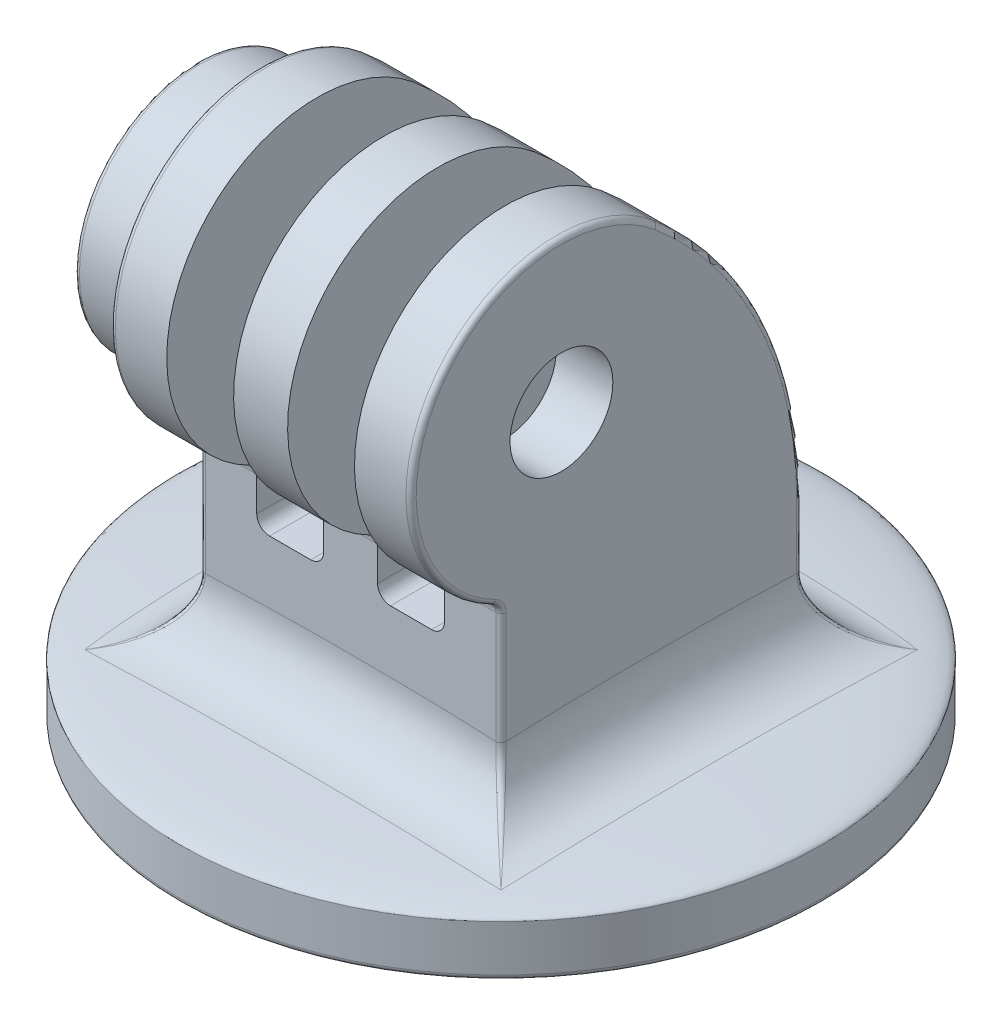
SolidWorks part; units mm, degrees
material "ABS"
ref_plane "Front Plane" through (0, 0, 0) normal (0, 0, 1) x (1, 0, 0)
ref_plane "Top Plane" through (0, 0, 0) normal (0, 1, 0) x (1, 0, 0)
ref_plane "Right Plane" through (0, 0, 0) normal (1, 0, 0) x (0, 0, -1)
sketch "Sketch1" plane through (0, 0, 0) normal (0, 1, 0) x (1, 0, 0)
  circle A0 centre (0, 0) radius 15.875
  dimension "D1" = 31.75
extrude "Boss-Extrude1" add sketch "Sketch1" along normal blind 2.54
ref_plane "Plane1" through (0, 3.175, 0) normal (0, 1, 0) x (-1, 0, 0)
dome "Dome1" faces to dome 1 distance 1.016 reverse direction no elliptical dome yes face at (0, 2.54, 15.875) parameters "D1"=1.016
sketch "Sketch2" plane through (0, 3.175, 0) normal (0, 1, 0) x (1, 0, 0)
  line L0 (0, 15.875) -> (0, -15.875) construction
  line L1 (15.875, 0) -> (-15.875, 0) construction
  line L3 (-7.4295, -7.4295) -> (7.4295, -7.4295)
  line L4 (-7.4295, -7.4295) -> (-7.4295, 7.4295)
  line L5 (-7.4295, 7.4295) -> (7.4295, 7.4295)
  line L6 (7.4295, -7.4295) -> (7.4295, 7.4295)
  line L7 (-7.4295, -7.4295) -> (7.4295, 7.4295) construction
  line L8 (-7.4295, 7.4295) -> (7.4295, -7.4295) construction
  circle A1 centre (0, 0) radius 15.875 construction
  point P7 (0, 0)
  dimension "D1" = 14.859
extrude "Boss-Extrude2" add sketch "Sketch2" along normal blind 6.35
sketch "Sketch3" plane through (7.4295, 0, 0) normal (1, 0, 0) x (0, 0, -1)
  line L0 (0, 9.525) -> (0, 0) construction
  line L1 (-7.4295, 9.525) -> (7.4295, 9.525) construction
  line L3 (-4.445, 9.525) -> (-4.445, 3.175) construction
  line L4 (-15.875, 0) -> (15.875, 0) construction
  line L5 (-7.4295, 9.525) -> (-7.4295, 11.8434)
  line L6 (7.4295, 9.525) -> (7.4295, 3.3016) construction
  line L7 (7.4295, 9.525) -> (-7.4295, 9.525)
  line L8 (0, 9.525) -> (0, 3.175) construction
  arc A0 (0.3272, 24.7441) -> (-7.7795, 12.4108) centre (-4.445, 19.05) ccw
  circle A1 centre (-4.445, 19.05) radius 2.54
  arc A2 (0.3272, 24.7441) -> (7.4295, 9.525) centre (-12.4279, 9.525) cw
  arc A3 (-7.7795, 12.4108) -> (-7.4295, 11.8434) centre (-8.0645, 11.8434) cw
  dimension "D2" = 14.859
  dimension "D3" = 5.08
  dimension "D5" = 0.635
  dimension "D4" = 19.05
  dimension "D1" = 4.445
extrude "Boss-Extrude3" add sketch "Sketch3" against normal up to surface (14.859 mm away) up to face at (-7.4295, 6.4463, 0.3453)
sketch "Sketch5" plane through (0, 0, -7.4295) normal (0, 0, -1) x (-1, 0, 0)
  line L0 (-4.6355, 26.4795) -> (-4.6355, 10.16)
  line L1 (7.4295, 26.4795) -> (-7.4295, 26.4795) construction
  line L2 (-7.4295, 9.525) -> (7.4295, 9.525) construction
  line L3 (-4.0005, 9.525) -> (-1.9685, 9.525)
  line L4 (-1.3335, 10.16) -> (-1.3335, 26.4795)
  line L5 (-1.3335, 26.4795) -> (-4.6355, 26.4795)
  line L6 (-7.4295, 24.7441) -> (-7.4295, 9.525) construction
  line L7 (0, 26.4795) -> (0, 0) construction
  line L8 (1.3335, 26.4795) -> (4.6355, 26.4795)
  line L9 (1.3335, 10.16) -> (1.3335, 26.4795)
  line L10 (4.0005, 9.525) -> (1.9685, 9.525)
  line L11 (4.6355, 26.4795) -> (4.6355, 10.16)
  arc A0 (4.6355, 10.16) -> (4.0005, 9.525) centre (4.0005, 10.16) cw
  arc A1 (1.3335, 10.16) -> (1.9685, 9.525) centre (1.9685, 10.16) ccw
  arc A2 (-1.3335, 10.16) -> (-1.9685, 9.525) centre (-1.9685, 10.16) cw
  arc A3 (-4.6355, 10.16) -> (-4.0005, 9.525) centre (-4.0005, 10.16) ccw
  point P20 (4.6355, 9.525)
  point P23 (1.3335, 9.525)
  point P26 (-1.3335, 9.525)
  point P29 (-4.6355, 9.525)
  dimension "D3" = 0.635
  dimension "D1" = 3.302
  dimension "D2" = 2.794
extrude "Cut-Extrude1" cut sketch "Sketch5" against normal through all
fillet "Fillet1" radius 3.175 4 edges at (-7.4295, 3.4335, 1.3813) (1.3813, 3.4335, 7.4295) (7.4295, 3.4335, -1.3813) (-1.3813, 3.4335, -7.4295)
fillet "Fillet2" radius 0.254 14 edges at (-7.853, 4.7068, 7.853) (-7.4295, 9.0792, 7.4295) (-7.4295, 12.1767, 7.524) (-7.4295, 23.1308, 10.6534) (-7.4295, 17.9224, -5.5665) (-7.4295, 7.92, -7.4295) (7.853, 4.7068, 7.853) (7.4295, 9.0792, 7.4295) (7.4295, 12.1767, 7.524) (7.4295, 23.1308, 10.6534) (7.4295, 17.9224, -5.5665) (7.4295, 7.92, -7.4295) (-7.853, 4.7068, -7.853) (7.853, 4.7068, -7.853)
fillet "Fillet3" radius 0.254 1 edges at (0, 0, 15.875)
sketch "Sketch6" plane through (0, 0, 0) normal (0, -1, 0) x (1, 0, 0)
  point P0 (0, 0)
hole_wizard "1/4-20 Tapped Hole1" positions "Sketch8" profile "Sketch9" tap size "1/4-20" standard "Ansi Inch"
sketch "Sketch8" plane through (0, 0, 0) normal (0, -1, 0) x (1, 0, 0)
  point P1 (0, 0)
sketch "Sketch9" plane through (0, 0, 0) normal (1, 0, 0) x (0, 0, -1)
  line L0 (0, 0) -> (0, 8.0701)
  line L1 (0, 8.0701) -> (2.5527, 7.62)
  line L2 (2.5527, 7.62) -> (2.5527, 0)
  line L5 (2.5527, 0) -> (0, 0)
  line L10 (0, 8.0701) -> (-2.5527, 7.62) construction
  line L11 (0, -6.35) -> (0, 107.95) construction
  dimension "Tap Drill Dia." = 5.1054
  dimension "Tap Drill Depth" = 7.62
  dimension "Drill Angle" = 160
cosmetic thread "Hole Thread1" parameters "D1"=6.35, "D2"=6.35
sketch "Sketch10" plane through (-7.4295, 0, 0) normal (-1, 0, 0) x (0, 0, 1)
  line L0 (4.445, 25.0825) -> (4.445, 13.0175) construction
  line L2 (4.445, 24.13) -> (0.0456, 21.59)
  line L3 (0.0456, 21.59) -> (0.0456, 16.51)
  line L4 (0.0456, 16.51) -> (4.445, 13.97)
  line L5 (4.445, 13.97) -> (8.8444, 16.51)
  line L6 (8.8444, 16.51) -> (8.8444, 21.59)
  line L7 (8.8444, 21.59) -> (4.445, 24.13)
  circle A0 centre (4.445, 19.05) radius 6.0325
  circle A1 centre (4.445, 19.05) radius 2.54 construction
  circle A2 centre (4.445, 19.05) radius 2.54 construction
  circle A3 centre (4.445, 19.05) radius 4.3994 construction
  dimension "D1" = 12.065
  dimension "D2" = 5.08
extrude "Boss-Extrude4" add sketch "Sketch10" along normal blind 3.175
fillet "Fillet4" radius 0.635 1 edges at (-7.4295, 19.05, -1.5875)
fillet "Fillet5" radius 0.254 1 edges at (-10.6045, 19.05, 10.4775)
fillet "Fillet6" radius 0.254 17 edges at (-10.6045, 19.05, 8.8444) (-10.6045, 15.24, 2.2453) (-10.6045, 19.05, 0.0456) (-10.6045, 22.86, 6.6447) (-9.017, 16.51, 8.8444) (-10.6045, 15.24, 6.6447) (-9.017, 13.97, 4.445) (-9.017, 21.59, 0.0456) (-10.6045, 22.86, 2.2453) (-9.017, 24.13, 4.445) (-7.4295, 19.05, 1.905) (-7.4295, 15.24, 6.6447) (-7.4295, 15.24, 2.2453) (-7.4295, 19.05, 0.0456) (-7.4295, 22.86, 2.2453) (-7.4295, 22.86, 6.6447) (-7.4295, 19.05, 8.8444)
